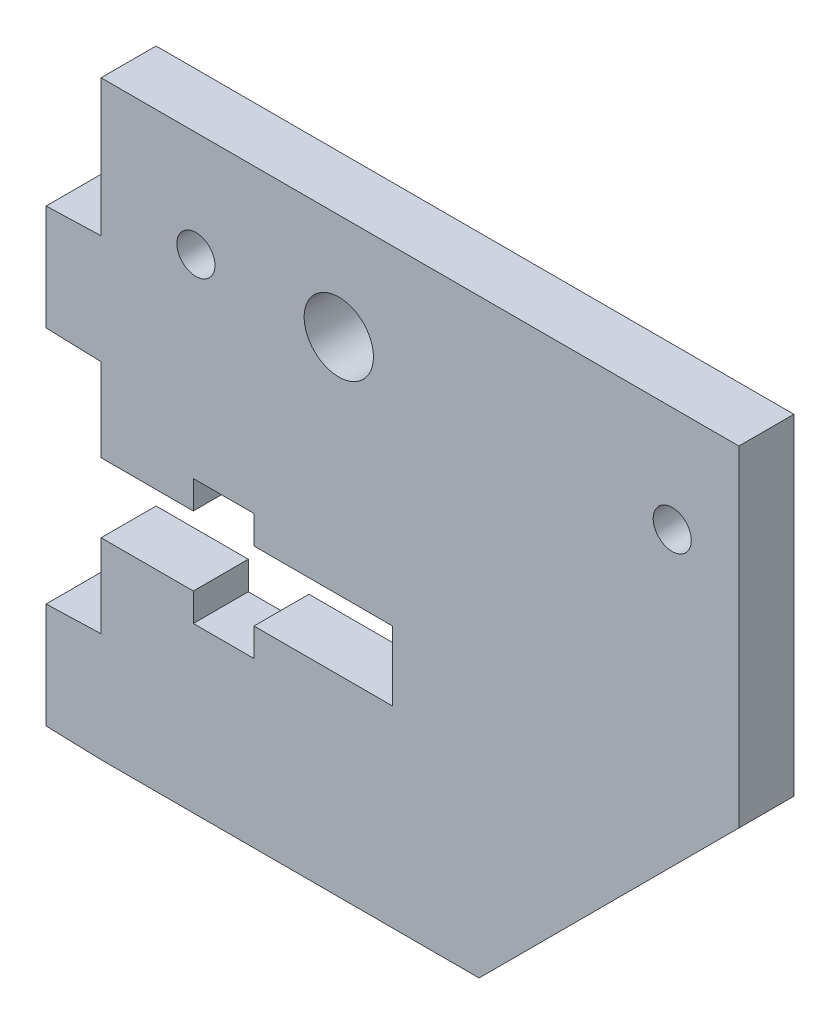
SolidWorks part; units mm, degrees
ref_plane "Front Plane" through (0, 0, 0) normal (0, 0, 1) x (1, 0, 0)
ref_plane "Top Plane" through (0, 0, 0) normal (0, 1, 0) x (1, 0, 0)
ref_plane "Right Plane" through (0, 0, 0) normal (1, 0, 0) x (0, 0, -1)
sketch "Sketch1" plane through (0, 0, 0) normal (0, 0, 1) x (1, 0, 0)
  line L0 (10.8, 34) -> (10.8, 21.8)
  line L1 (0, 0) -> (40, 0)
  line L2 (0, 0) -> (0, 6.1)
  line L3 (3.175, 34) -> (10.8, 34)
  line L4 (40, 0) -> (40, 34)
  line L5 (10.8, 21.8) -> (34, 21.8)
  line L6 (34, 21.8) -> (34, 34)
  line L7 (34, 34) -> (40, 34)
  line L8 (-11.825, 17) -> (40, 17) construction
  line L9 (0, 19.9) -> (3.175, 19.9)
  line L10 (12, 15) -> (20, 15)
  line L11 (0, 6.1) -> (3.175, 6.1)
  line L12 (3.175, 19.9) -> (3.175, 15)
  line L13 (3.175, 15) -> (8.5, 15)
  line L14 (8.5, 11) -> (8.5, 9.375)
  line L15 (3.175, 11) -> (8.5, 11)
  line L16 (20, 15) -> (20, 11)
  line L17 (8.5, 16.625) -> (12, 16.625)
  line L18 (8.5, 16.625) -> (8.5, 15)
  line L19 (8.5, 9.375) -> (12, 9.375)
  line L20 (12, 16.625) -> (12, 15)
  line L21 (3.175, 11) -> (3.175, 6.1)
  line L22 (12, 11) -> (12, 9.375)
  line L23 (0, 19.9) -> (0, 26)
  line L24 (12, 11) -> (20, 11)
  line L25 (10.8, 34) -> (34, 34)
  line L26 (0, 26) -> (3.175, 26)
  line L27 (0, 26) -> (0, 34)
  line L28 (0, 34) -> (3.175, 34)
  line L29 (3.175, 26) -> (3.175, 34)
  line L30 (0, 26) -> (3.175, 26.1)
  line L31 (0, 19.9) -> (3.175, 19.8)
  line L32 (0, 6.1) -> (3.175, 6.2)
  line L33 (3.175, -0.1) -> (0, 0)
  line L34 (0, 0) -> (40, 0)
  line L35 (0, 0) -> (0, -0.1)
  line L36 (0, -0.1) -> (40, -0.1)
  line L37 (40, 0) -> (40, -0.1)
  circle A0 centre (8.65, 27.9) radius 1.1
  circle A1 centre (36.15, 27.9) radius 1.1
  circle A2 centre (16.9, 27.9) radius 2
  dimension "D8" = 2.2
  dimension "D9" = 2.2
  dimension "D24" = 4
  dimension "D1" = 34
  dimension "D2" = 40
  dimension "D3" = 12.2
  dimension "D4" = 23.2
  dimension "D5" = 6
  dimension "D6" = 27.5
  dimension "D7" = 6.1
  dimension "D10" = 2.15
  dimension "D11" = 19.9
  dimension "D12" = 6.1
  dimension "D13" = 3.175
  dimension "D14" = 4
  dimension "D15" = 7.25
  dimension "D16" = 15
  dimension "D17" = 16.625
  dimension "D18" = 3.5
  dimension "D19" = 20
  dimension "D20" = 8.5
  dimension "D21" = 6.1
  dimension "D22" = 3.175
  dimension "D23" = 16.9
  dimension "D25" = 0.1
  dimension "D26" = 0.1
  dimension "D27" = 0.1
  dimension "D28" = 0.1
extrude "Boss-Extrude1" add sketch "Sketch1" along normal blind 3.175 contours L12 L8 L4 L7 L6 L5 L0 L3 L29 L26 L23 L9 A0 A1 | L8 L12 L13 L18 L17 L20 L10 L16 L24 L22 L19 L14 L15 L21 L11 L2 L1 L4 | L25 L0 L5 L6 A2 | L30 L26 L29 | L9 L31 L12 | L37 L1 L33 L36 | L32 L11 L21 region at (22.6555, 27.9, 0) region at (10.3654, 27.9, 0) region at (2.1167, 26.0333, 0) region at (22.3191, 7.689, 0) region at (2.1167, 19.8667, 0) region at (20.7828, -0.0493, 0) region at (2.1167, 6.1333, 0)
chamfer "Chamfer1" distance 15 angle 45 1 edges at (40, -0.1, 1.5875)
